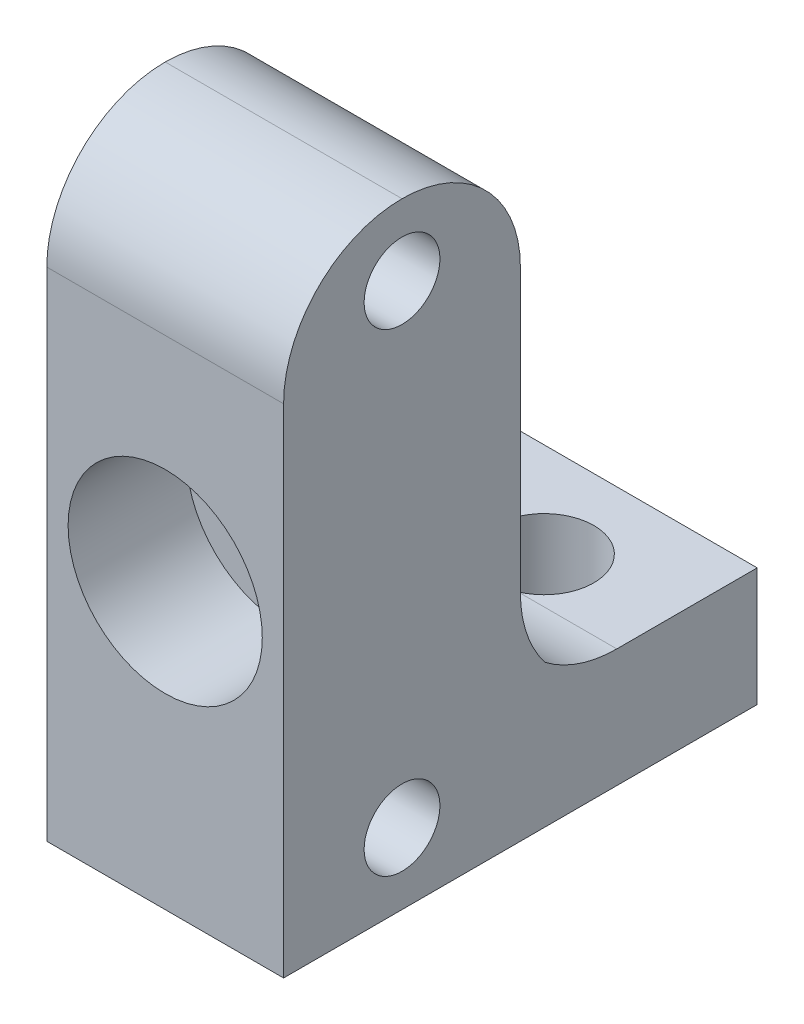
SolidWorks part; units mm, degrees
ref_plane "Plan de face" through (0, 0, 0) normal (0, 0, 1) x (1, 0, 0)
ref_plane "Plan de dessus" through (0, 0, 0) normal (0, 1, 0) x (1, 0, 0)
ref_plane "Plan de droite" through (0, 0, 0) normal (1, 0, 0) x (0, 0, -1)
sketch "Esquisse1" plane through (0, 0, 0) normal (0, 0, 1) x (1, 0, 0)
  line L1 (0, 0) -> (10, 0)
  line L2 (0, 0) -> (0, 26)
  line L3 (0, 26) -> (10, 26)
  line L4 (10, 0) -> (10, 26)
  circle A0 centre (5, 12) radius 4.1
  dimension "D1" = 8.2
  dimension "D2" = 12
  dimension "D3" = 26
  dimension "D4" = 5
  dimension "D5" = 5
extrude "Boss.-Extru.1" add sketch "Esquisse1" along normal blind 10
sketch "Esquisse2" plane through (0, 0, 0) normal (-1, 0, 0) x (0, 0, 1)
  line L0 (0, 26) -> (0, 0) construction
  line L1 (10, 26) -> (0, 26) construction
  circle A0 centre (5, 23) radius 1.6
  circle A1 centre (5, 3) radius 1.6
  dimension "D1" = 3.2
  dimension "D2" = 3.2
  dimension "D3" = 5
  dimension "D4" = 5
  dimension "D5" = 20
  dimension "D6" = 3
extrude "Enlèv. mat.-Extru.1" cut sketch "Esquisse2" against normal blind 10
sketch "Esquisse3" plane through (0, 0, 0) normal (0, -1, 0) x (1, 0, 0)
  line L19 (0, 10) -> (0, 0) construction
  line L20 (10, 0) -> (0, 0)
  line L21 (10, 0) -> (10, -10)
  line L22 (10, -10) -> (0, -10)
  line L23 (0, 0) -> (0, -10)
  dimension "D1" = 0
  dimension "D2" = 10
extrude "Boss.-Extru.2" add sketch "Esquisse3" against normal blind 5
chamfer "Chanfrein1" distance 2 angle 45 1 edges at (5, 5, 0)
sketch "Esquisse4" plane through (0, 5, 0) normal (0, 1, 0) x (1, 0, 0)
  line L0 (0, 2) -> (10, 10) construction
  circle A0 centre (5, 6) radius 2.1
  dimension "D1" = 4.2
extrude "Enlèv. mat.-Extru.2" cut sketch "Esquisse4" against normal blind 5
sketch "Esquisse5" plane through (0, 0, 0) normal (0, 0, -1) x (-1, 0, 0)
  circle A0 centre (-5, 12) radius 4.1067
extrude "Boss.-Extru.3" add sketch "Esquisse5" against normal blind 5
fillet "Congé1" radius 5 4 edges at (5, 26, 10) (5, 26, 0) (5, 7, 0) (5, 5, -2)
